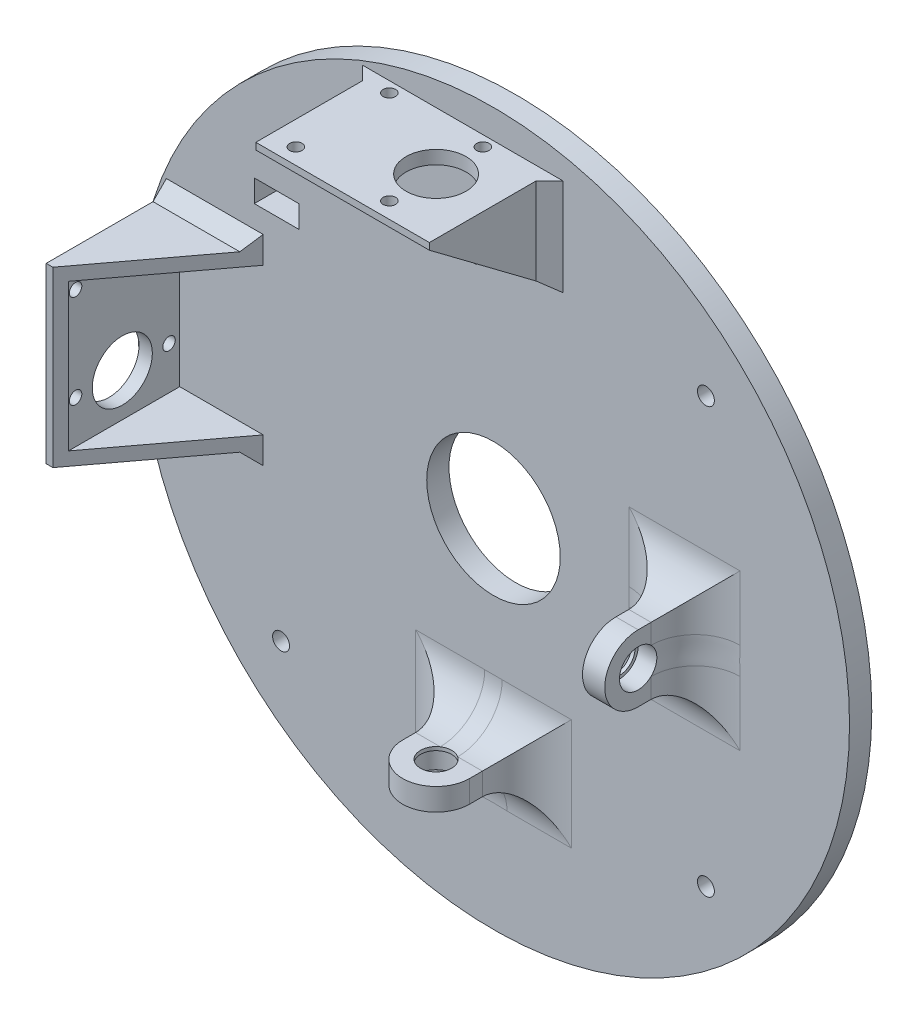
SolidWorks part; units mm, degrees
ref_plane "正面" through (0, 0, 0) normal (0, 0, 1) x (1, 0, 0)
ref_plane "平面" through (0, 0, 0) normal (0, 1, 0) x (1, 0, 0)
ref_plane "右側面" through (0, 0, 0) normal (1, 0, 0) x (0, 0, -1)
sketch "ｽｹｯﾁ5" plane through (0, 0, 0) normal (0, 1, 0) x (1, 0, 0)
  line L0 (-73.5, -32) -> (-73.5, 0)
  line L1 (-73.5, 0) -> (-49.5, 0)
  line L2 (-49.5, 0) -> (-73.5, -32)
  line L3 (-55, 0) -> (55, 0) construction
  dimension "D1" = 24
  dimension "D2" = 32
  dimension "D3" = 49.5
extrude "ﾎﾞｽ - 押し出し3" add sketch "ｽｹｯﾁ5" against normal blind 39 from offset 26.4
shell "ｼｪﾙ2" thickness 3 removed face at (-61.5, 6.9, 16)
sketch "ｽｹｯﾁ7" plane through (-70.5, 0, 0) normal (1, 0, 0) x (0, 0, -1)
  line L0 (-3, -9.6) -> (-3, 23.4) construction
  line L1 (-26.4, 0) -> (-5.4, 0) construction
  line L2 (-26.4, 0) -> (-26.4, 21) construction
  line L3 (-26.4, 21) -> (-5.4, 21) construction
  line L4 (-5.4, 0) -> (-5.4, 21) construction
  line L5 (-3, 23.4) -> (-28, 23.4) construction
  circle A0 centre (-15.9, 0) radius 6.75
  circle A1 centre (-26.4, 0) radius 1.4
  circle A2 centre (-5.4, 0) radius 1.4
  circle A3 centre (-5.4, 21) radius 1.4
  circle A4 centre (-26.4, 21) radius 1.4
  point P10 (-15.9, 0)
  dimension "D3" = 2.8
  dimension "D6" = 13.5
  dimension "D1" = 21
  dimension "D2" = 21
  dimension "D4" = 2.4
  dimension "D5" = 2.4
extrude "ｶｯﾄ - 押し出し5" cut sketch "ｽｹｯﾁ7" against normal through all
sketch "ｽｹｯﾁ12" plane through (0, 0, 0) normal (0, 0, 1) x (1, 0, 0)
  line L0 (-73.5, -12.6) -> (-73.5, 26.4) construction
  line L1 (-73.5, -12.6) -> (-73.5, 26.4)
  line L2 (-73.5, 26.4) -> (-68.2389, 26.4)
  line L3 (-49.5, 26.4) -> (-73.5, 26.4) construction
  line L4 (-68.2389, 26.4) -> (-68.2389, -12.6)
  line L5 (-68.2389, -12.6) -> (-73.5, -12.6)
  line L6 (-49.5, -12.6) -> (-73.5, -12.6) construction
extrude "ｶｯﾄ - 押し出し10" cut sketch "ｽｹｯﾁ12" along normal blind 36 from offset 30
sketch "ｽｹｯﾁ1" plane through (0, 0, 0) normal (0, 0, 1) x (1, 0, 0)
  line L1 (56.5685, -56.5685) -> (-56.5685, -56.5685) construction
  line L2 (56.5685, -56.5685) -> (56.5685, 56.5685) construction
  line L3 (56.5685, 56.5685) -> (-56.5685, 56.5685) construction
  line L4 (-56.5685, -56.5685) -> (-56.5685, 56.5685) construction
  line L5 (56.5685, -56.5685) -> (-56.5685, 56.5685) construction
  line L6 (56.5685, 56.5685) -> (-56.5685, -56.5685) construction
  circle A0 centre (0, 0) radius 80
  point P0 (0, 0)
  dimension "D1" = 160
extrude "ﾎﾞｽ - 押し出し1" add sketch "ｽｹｯﾁ1" along normal blind 3 and the other way blind 2 contours A0
sketch "ｽｹｯﾁ3" plane through (0, 0, 0) normal (0, 0, 1) x (1, 0, 0)
  circle A0 centre (0, 0) radius 15
  dimension "D1" = 30
extrude "ｶｯﾄ - 押し出し4" cut sketch "ｽｹｯﾁ3" against normal through all both and the other way through all
ref_plane "平面1" through (0, -40.4, 0) normal (0, 1, 0) x (1, 0, 0)
sketch "ｽｹｯﾁ10" plane through (-147.416, -40.4, 0) normal (0, 1, 0) x (1, 0, 0)
  line L0 (139.916, 0) -> (154.916, 0)
  line L1 (154.916, 0) -> (154.916, -15.9)
  line L2 (139.916, 0) -> (139.916, -15.9)
  line L3 (59.416, 0) -> (235.416, 0) construction
  arc A2 (139.916, -15.9) -> (154.916, -15.9) centre (147.416, -15.9) ccw
  point P7 (147.416, 0)
  dimension "D1" = 15
  dimension "D2" = 15.9
extrude "ﾎﾞｽ - 押し出し5" add sketch "ｽｹｯﾁ10" against normal blind 5
sketch "ｽｹｯﾁ11" plane through (-147.416, -40.4, 0) normal (0, 1, 0) x (1, 0, 0)
  circle A0 centre (147.416, -15.9) radius 4.2
  arc A1 (139.916, -15.9) -> (154.916, -15.9) centre (147.416, -15.9) ccw construction
  dimension "D1" = 8.4
extrude "ｶｯﾄ - 押し出し8" cut sketch "ｽｹｯﾁ11" along normal up to surface (-5 mm away) up to face at (0, -45.4, 11.325)
sketch "ｽｹｯﾁ14" plane through (0, -40.4, 0) normal (0, -1, 0) x (1, 0, 0)
  circle A0 centre (0, 15.9) radius 4.2 construction
  circle A1 centre (0, 15.9) radius 4.2
  circle A2 centre (0, 15.9) radius 3.5
  dimension "D1" = 7
extrude "ﾎﾞｽ - 押し出し6" add sketch "ｽｹｯﾁ14" along normal blind 0.8
fillet "ﾌｨﾚｯﾄ1" radius 10 4 edges at (7.5, -42.9, 3) (-7.5, -42.9, 3) (0, -45.4, 3) (0, -40.4, 3)
ref_plane "平面3" through (0, 0, 0) normal (0.7071, 0.7071, 0) x (-0.7071, 0.7071, 0)
mirror "ﾐﾗｰ1" about plane through (0, 0, 0) normal (0.7071, 0.7071, 0) of bodies 135 129
sketch "ｽｹｯﾁ15" plane through (0, 0, 3) normal (0, 0, 1) x (1, 0, 0)
  line L0 (-6.75, 70.5) -> (6.75, 70.5) construction
  line L1 (-3.85, 53.8) -> (-17.65, 53.8)
  line L2 (-3.85, 53.8) -> (-3.85, 47.5)
  line L3 (-3.85, 47.5) -> (-17.65, 47.5)
  line L4 (-17.65, 53.8) -> (-17.65, 47.5)
  line L5 (-3.85, 53.8) -> (-17.65, 47.5) construction
  line L6 (-3.85, 47.5) -> (-17.65, 53.8) construction
  line L7 (-6.75, 70.5) -> (6.75, 70.5)
  point P0 (-10.75, 50.65)
  point P7 (0, 70.5)
  dimension "D1" = 3.85
  dimension "D2" = 23
  dimension "D3" = 17.65
  dimension "D4" = 6.3
extrude "ｶｯﾄ - 押し出し11" cut sketch "ｽｹｯﾁ15" along normal through all both and the other way through all contours L1 L4 L3 L2 region at (-10.75, 50.65, 3)
sketch "ｽｹｯﾁ16" plane through (0, 0, 3) normal (0, 0, 1) x (1, 0, 0)
  line L0 (56.5685, 56.5685) -> (-56.5685, -56.5685) construction
  circle A0 centre (0, 0) radius 67.5 construction
  circle A1 centre (-47.7297, -47.7297) radius 1.9
  circle A3 centre (-47.7297, 47.7297) radius 1.9
  circle A4 centre (47.7297, 47.7297) radius 1.9
  circle A5 centre (47.7297, -47.7297) radius 1.9
  point P14 (0, 0)
  dimension "D1" = 135
  dimension "D3" = 3.8
  dimension "D2" = 4
extrude "ｶｯﾄ - 押し出し12" cut sketch "ｽｹｯﾁ16" against normal through all both and the other way through all
chamfer "面取り1" distance 3 angle 45 4 edges at (12.6, 62.625, 3) (-26.4, 62.625, 3) (-62.625, 26.4, 3) (-62.625, -12.6, 3)
sketch "ｽｹｯﾁ17" plane through (0, 0, 3) normal (0, 0, 1) x (1, 0, 0)
  line L1 (-53.75, 34.4) -> (-43.75, 34.4)
  line L2 (-53.75, 34.4) -> (-53.75, 39.4)
  line L3 (-53.75, 39.4) -> (-43.75, 39.4)
  line L4 (-43.75, 34.4) -> (-43.75, 39.4)
  line L5 (-53.75, 34.4) -> (-43.75, 39.4) construction
  line L6 (-53.75, 39.4) -> (-43.75, 34.4) construction
  line L7 (-73.5, 29.4) -> (-51.75, 29.4) construction
  line L8 (-51.75, 29.4) -> (-51.75, 23.4) construction
  point P0 (-48.75, 36.9)
  dimension "D1" = 5
  dimension "D2" = 10
  dimension "D3" = 5
  dimension "D4" = 2
extrude "ｶｯﾄ - 押し出し13" cut sketch "ｽｹｯﾁ17" against normal blind 10
